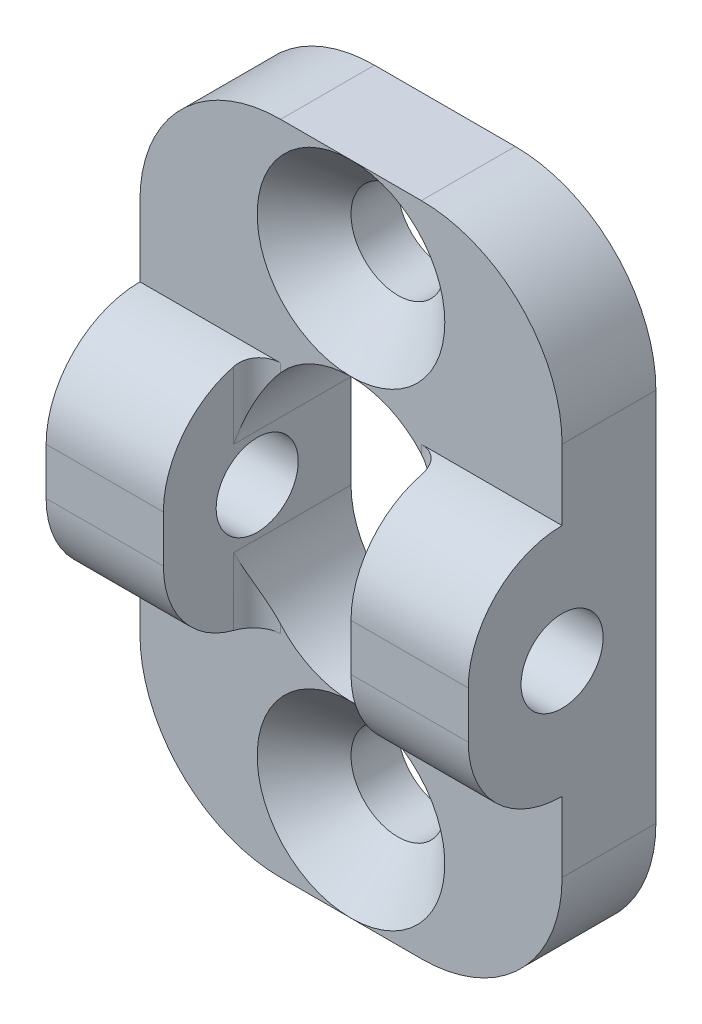
SolidWorks part; units mm, degrees
ref_plane "Plan de face" through (0, 0, 0) normal (0, 0, 1) x (1, 0, 0)
ref_plane "Plan de dessus" through (0, 0, 0) normal (0, 1, 0) x (1, 0, 0)
ref_plane "Plan de droite" through (0, 0, 0) normal (1, 0, 0) x (0, 0, -1)
sketch "Esquisse1" plane through (0, 0, 0) normal (0, 0, 1) x (1, 0, 0)
  line L1 (0, 0) -> (18, 0)
  line L2 (0, 0) -> (0, 28)
  line L3 (0, 28) -> (18, 28)
  line L4 (18, 0) -> (18, 28)
  dimension "D1" = 18
  dimension "D2" = 28
extrude "Boss.-Extru.1" add sketch "Esquisse1" along normal blind 4
sketch "Esquisse2" plane through (0, 0, 4) normal (0, 0, 1) x (1, 0, 0)
  line L0 (18, 14) -> (0, 14) construction
  line L1 (18, 0) -> (18, 28) construction
  line L2 (0, 28) -> (0, 0) construction
  line L3 (0, 9) -> (18, 9)
  line L4 (0, 9) -> (0, 19)
  line L5 (0, 19) -> (18, 19)
  line L6 (18, 9) -> (18, 19)
  line L7 (0, 9) -> (18, 19) construction
  line L8 (0, 19) -> (18, 9) construction
  point P4 (0, 10)
  point P5 (9, 14)
  dimension "D1" = 10
extrude "Boss.-Extru.2" add sketch "Esquisse2" along normal blind 4
sketch "Esquisse3" plane through (0, 0, 8) normal (0, 0, 1) x (1, 0, 0)
  line L0 (0, 14) -> (18, 14) construction
  line L1 (0, 19) -> (0, 9) construction
  line L2 (18, 9) -> (18, 19) construction
  line L3 (0, 9) -> (18, 9) construction
  line L4 (5, 19) -> (13, 19)
  line L5 (5, 19) -> (5, 9)
  line L6 (5, 9) -> (13, 9)
  line L7 (13, 19) -> (13, 9)
  line L8 (5, 19) -> (13, 9) construction
  line L9 (5, 9) -> (13, 19) construction
  point P6 (9, 14)
  dimension "D1" = 5
extrude "Enlèv. mat.-Extru.1" cut sketch "Esquisse3" against normal up to surface (4 mm away) up to face at (9, 23.5, 4)
sketch "Esquisse4" plane through (0, 0, 4) normal (0, 0, 1) x (1, 0, 0)
  line L0 (5, 14) -> (13, 14) construction
  line L1 (5, 19) -> (5, 9) construction
  line L2 (13, 9) -> (13, 19) construction
  line L3 (9, 12) -> (9, 16) construction
  line L4 (5, 12) -> (5, 16)
  line L5 (13, 12) -> (13, 16)
  line L7 (5, 19) -> (5, 9) construction
  arc A0 (5, 12) -> (13, 12) centre (9, 12) ccw
  arc A1 (13, 16) -> (5, 16) centre (9, 16) ccw
  point P5 (9, 14)
  dimension "D1" = 4
extrude "Enlèv. mat.-Extru.2" cut sketch "Esquisse4" against normal through all both and the other way through all
sketch "Esquisse5" plane through (18, 0, 0) normal (1, 0, 0) x (0, 0, -1)
  line L0 (-8, 14) -> (0, 14) construction
  line L1 (-8, 9) -> (-8, 19) construction
  line L2 (0, 0) -> (0, 28) construction
  circle A0 centre (-4, 14) radius 1.75
  dimension "D1" = 3.5
extrude "Enlèv. mat.-Extru.3" cut sketch "Esquisse5" against normal through all both and the other way through all
sketch "Esquisse6" plane through (0, 0, 4) normal (0, 0, 1) x (1, 0, 0)
  line L0 (9, 28) -> (9, 14) construction
  line L1 (18, 28) -> (0, 28) construction
  line L2 (9, 14) -> (18, 14) construction
  line L3 (18, 9) -> (18, 19) construction
  circle A0 centre (9, 24) radius 2
  circle A1 centre (9, 4) radius 2
  dimension "D1" = 4
  dimension "D2" = 10
extrude "Enlèv. mat.-Extru.4" cut sketch "Esquisse6" against normal through all both and the other way through all
chamfer "Chanfrein1" distance 2 angle 45 2 edges at (7, 24, 4) (7, 4, 4)
fillet "Congé1" radius 4 4 edges at (2.5, 9, 8) (2.5, 19, 8) (15.5, 19, 8) (15.5, 9, 8)
fillet "Congé2" radius 6 4 edges at (18, 28, 2) (0, 28, 2) (0, 0, 2) (18, 0, 2)
fillet "Congé3" radius 1 4 edges at (13, 17.5, 4) (5, 17.5, 4) (13, 10.5, 4) (5, 10.5, 4)
